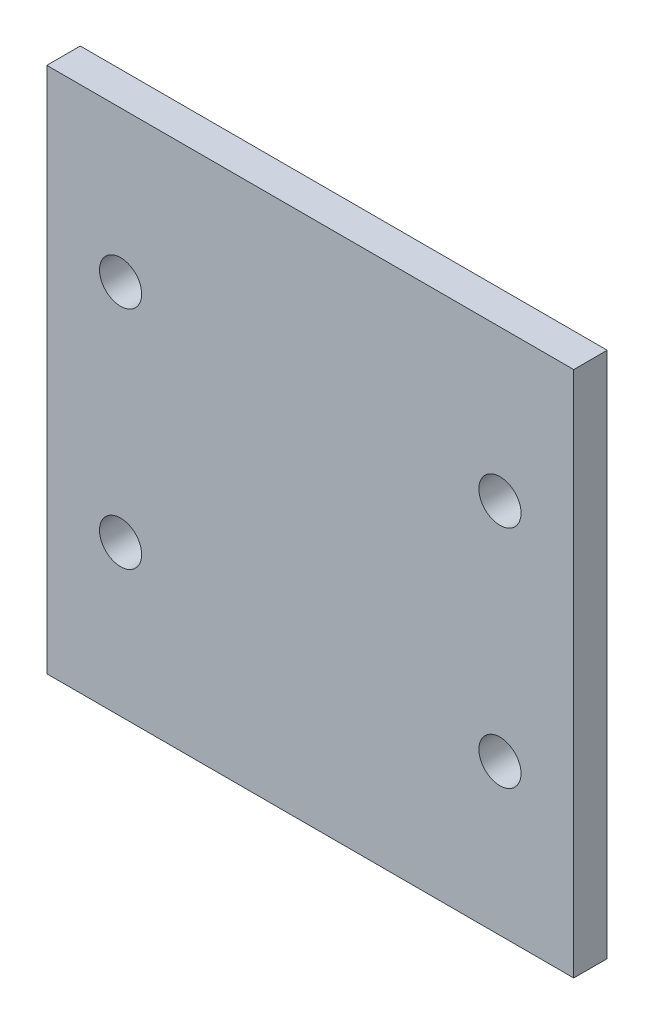
SolidWorks part; units mm, degrees
material "Alliage 1060"
ref_plane "Plan de face" through (0, 0, 0) normal (0, 0, 1) x (1, 0, 0)
ref_plane "Plan de dessus" through (0, 0, 0) normal (0, 1, 0) x (1, 0, 0)
ref_plane "Plan de droite" through (0, 0, 0) normal (1, 0, 0) x (0, 0, -1)
sketch "Esquisse1" plane through (0, 0, 0) normal (0, 0, 1) x (1, 0, 0)
  line L1 (-12.5, -12.5) -> (12.5, -12.5)
  line L2 (-12.5, -12.5) -> (-12.5, 12.5)
  line L3 (-12.5, 12.5) -> (12.5, 12.5)
  line L4 (12.5, -12.5) -> (12.5, 12.5)
  line L5 (-12.5, -12.5) -> (12.5, 12.5) construction
  line L6 (-12.5, 12.5) -> (12.5, -12.5) construction
  line L7 (9, 5.35) -> (-9, 5.35) construction
  line L8 (9, 5.35) -> (9, -5.35) construction
  line L9 (9, -5.35) -> (-9, -5.35) construction
  line L10 (-9, 5.35) -> (-9, -5.35) construction
  line L11 (9, 5.35) -> (-9, -5.35) construction
  line L12 (9, -5.35) -> (-9, 5.35) construction
  circle A0 centre (0, 0) radius 4 construction
  circle A1 centre (-9, 5.35) radius 1
  circle A2 centre (9, 5.35) radius 1
  circle A3 centre (-9, -5.35) radius 1
  circle A4 centre (9, -5.35) radius 1
  point P0 (0, 0)
  dimension "D3" = 2
  dimension "D5" = 10.7
  dimension "D7" = 8
  dimension "D1" = 25
  dimension "D2" = 25
  dimension "D4" = 18
extrude "Boss.-Extru.1" add sketch "Esquisse1" along normal blind 1.5875
